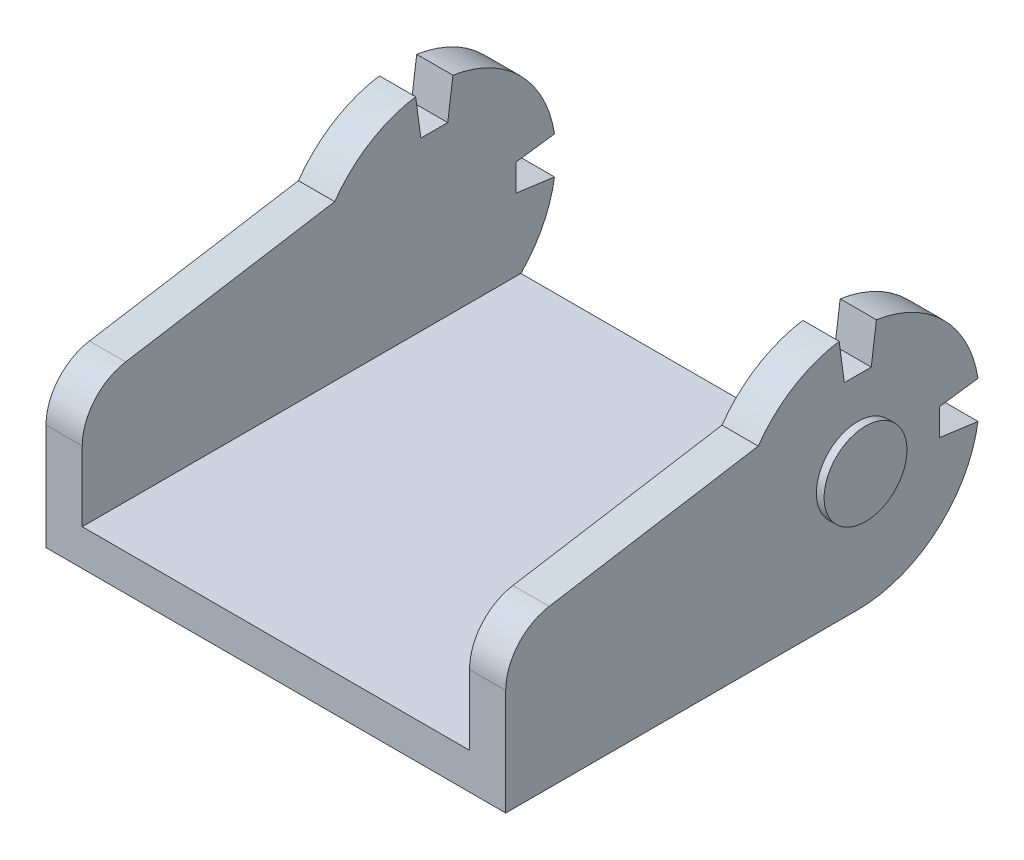
SolidWorks part; units mm, degrees
material "ABS PC"
ref_plane "Front Plane" through (0, 0, 0) normal (0, 0, 1) x (1, 0, 0)
ref_plane "Top Plane" through (0, 0, 0) normal (0, 1, 0) x (1, 0, 0)
ref_plane "Right Plane" through (0, 0, 0) normal (1, 0, 0) x (0, 0, -1)
sketch "Profile Sketch" plane through (0, 0, 0) normal (0, 0, 1) x (1, 0, 0)
  line L0 (-22.2, -11.75) -> (22.2, -11.75)
  line L1 (22.2, -11.75) -> (22.2, 11.75)
  line L2 (22.2, 11.75) -> (18.7, 11.75)
  line L3 (18.7, 11.75) -> (18.7, -8.25)
  line L4 (18.7, -8.25) -> (-18.7, -8.25)
  line L5 (-18.7, -8.25) -> (-18.7, 11.75)
  line L6 (-18.7, 11.75) -> (-22.2, 11.75)
  line L7 (-22.2, 11.75) -> (-22.2, -11.75)
  point P0 (0, -11.75)
  dimension "Outer Width Ba" = 44.4
  dimension "Outer Height Ha" = 23.5
  dimension "Inner Width Bi" = 37.4
  dimension "D1" = 3.5
  dimension "D2" = 11.75
extrude "Body" add sketch "Profile Sketch" along normal blind 34 and the other way blind 15
sketch "Pivot Pin R Sketch" plane through (0, 0, 0) normal (1, 0, 0) x (0, 0, -1)
  line L0 (15, -11.75) -> (15, 11.75) construction
  circle A0 centre (0, 0) radius 4
  point P5 (15, 0)
  dimension "D1" = 8
extrude "Pivot Pin R" add sketch "Pivot Pin R Sketch" along normal blind 4.25 from offset 18.7
mirror "Pivot Pin L" about plane through (0, 0, 0) normal (1, 0, 0) of "Pivot Pin R"
sketch "Outside Shape Cut Out Sketch" plane through (0, 0, 0) normal (1, 0, 0) x (0, 0, -1)
  line L0 (15, -11.75) -> (15, 11.75) construction
  line L1 (15, -11.75) -> (-34, -11.75) construction
  line L2 (-29.8094, 3.4375) -> (-9.6177, 6.75)
  line L3 (-34, -1.4966) -> (-34, -11.75)
  line L4 (-34, -11.75) -> (0, -11.75)
  line L5 (-34, -11.75) -> (-34, 11.75) construction
  line L12 (11.6113, 1.8) -> (7.9, 1.3)
  line L13 (11.6113, -1.8) -> (7.9, -1.3)
  line L14 (7.9, -1.3) -> (7.9, 1.3)
  line L15 (1.8, 11.6113) -> (1.3, 7.9)
  line L16 (1.3, 7.9) -> (-1.3, 7.9)
  line L17 (-1.3, 7.9) -> (-1.8, 11.6113)
  line L18 (-36, 11.75) -> (15, 11.75)
  line L19 (-36, 11.75) -> (-36, -13.75)
  line L20 (-36, -13.75) -> (15, -13.75)
  line L21 (15, 11.75) -> (15, -13.75)
  line L22 (-36, 11.75) -> (15, -13.75) construction
  line L23 (-36, -13.75) -> (15, 11.75) construction
  line L24 (15, 11.75) -> (-34, 11.75) construction
  line L25 (0, 0) -> (11.6113, 0) construction
  line L26 (11.6113, 1.8) -> (11.6113, -1.8) construction
  line L27 (0, 0) -> (0, 11.6113) construction
  line L28 (-1.8, 11.6113) -> (1.8, 11.6113) construction
  arc A0 (0, -11.75) -> (11.6113, -1.8) centre (0, 0) ccw
  arc A1 (-1.8, 11.6113) -> (-9.6177, 6.75) centre (0, 0) ccw
  arc A2 (11.6113, 1.8) -> (1.8, 11.6113) centre (0, 0) ccw
  arc A3 (-29.8094, 3.4375) -> (-34, -1.4966) centre (-29, -1.4966) ccw
  circle A4 centre (0, 0) radius 4 construction
  point P2 (7.9, 0)
  point P19 (11.6113, 0)
  point P20 (0, 7.9)
  point P22 (0, 11.6113)
  point P23 (0, 0)
  point P28 (-34, 2.75)
  point P29 (-10.5, -1)
  dimension "D5" = 5
  dimension "D1" = 9
  dimension "D2" = 5
  dimension "D3" = 7.9
  dimension "D4" = 2.6
  dimension "D6" = 2
  dimension "D7" = 2
  dimension "D8" = 3.6
  dimension "D9" = 7.9
extrude "Outside Shape Cut Out" cut sketch "Outside Shape Cut Out Sketch" against normal through all both and the other way through all
equation "\"A\" = 10"
equation "\"B\" = 15"
equation "\"C\" = 32"
equation "\"E\" = 8"
equation "\"F\" = 39"
equation "\"C@Body\"=\"C\"+2"
equation "\"D2@Sketch5\"=\"B\""
equation "\"D3@Sketch5\"=\"F\"/2"
equation "\"D4@Sketch5\"=\"E\""
equation "\"D2@Sketch3\"=\"E\""
equation "\"D3@Sketch3\"=\"A\""
equation "\"D4@Sketch3\"=\"F\"/2"
equation "\"D2@Sketch1\"=\"B\""
equation "\"D3@Sketch1\"=\"F\"/2"
equation "\"Inner Width Bi\" = 37.4"
equation "\"Inner Width Bi@Profile Sketch\"=\"Inner Width Bi\""
equation "\"D19@Pivot Pin R\"=\"Inner Width Bi\"/2"
equation "\"D19@Outside Shape Cut Out R\"=\"Inner Width Bi\"/2+2.3"
